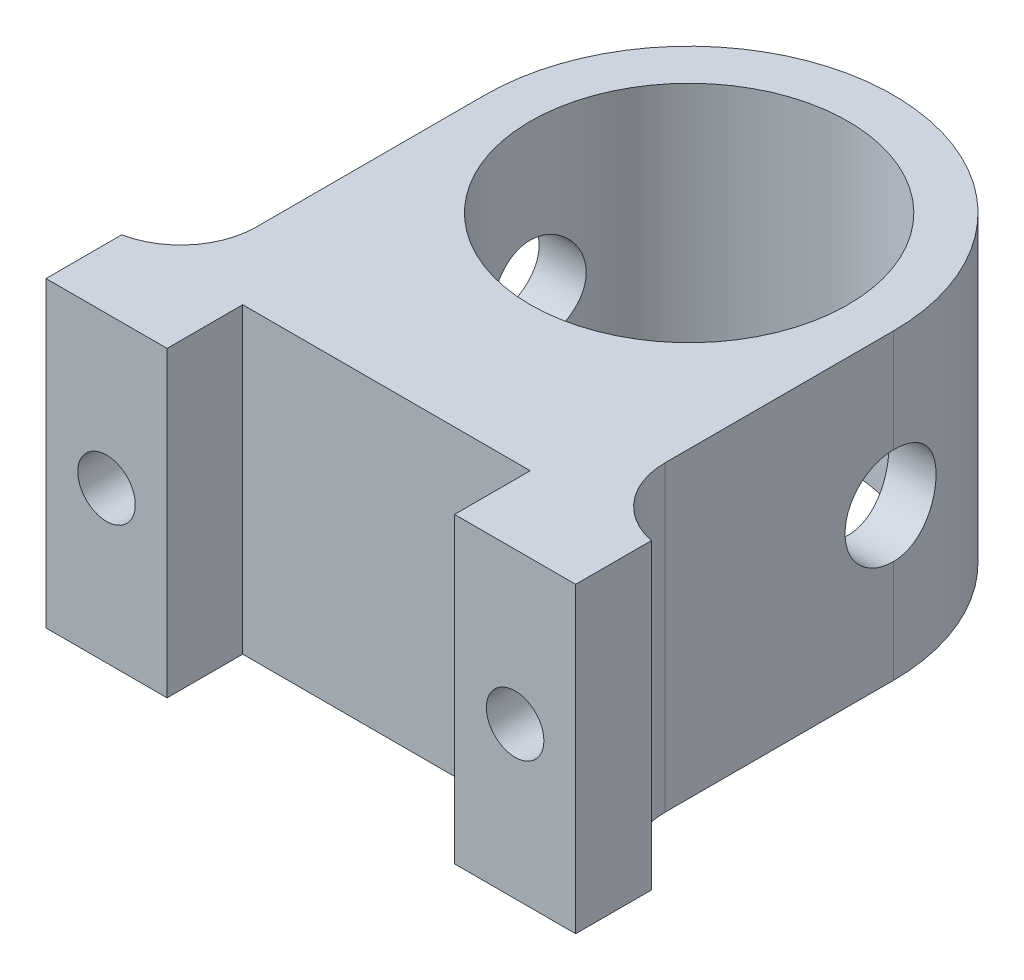
SolidWorks part; units mm, degrees
ref_plane "前视基准面" through (0, 0, 0) normal (0, 0, 1) x (1, 0, 0)
ref_plane "上视基准面" through (0, 0, 0) normal (0, 1, 0) x (1, 0, 0)
ref_plane "右视基准面" through (0, 0, 0) normal (1, 0, 0) x (0, 0, -1)
sketch "草图1" plane through (0, 0, 0) normal (0, 1, 0) x (1, 0, 0)
  circle A0 centre (0, 0) radius 10.5
  circle A1 centre (0, 0) radius 13.5
  dimension "D1" = 21
  dimension "D2" = 3
extrude "凸台-拉伸1" add sketch "草图1" along normal blind 20
ref_plane "基准面1" through (0, 0, 20) normal (0, 0, 1) x (1, 0, 0)
sketch "草图5" plane through (0, 0, 20) normal (0, 0, 1) x (1, 0, 0)
  line L0 (-13.5, 0) -> (-13.5, 20)
  line L1 (-13.5, 0) -> (13.5, 0)
  line L2 (0, 0) -> (0, 20) construction
  line L3 (-13.5, 20) -> (13.5, 20)
  line L4 (13.5, 0) -> (13.5, 20)
  dimension "D1" = 20
  dimension "D2" = 13.5
extrude "凸台-拉伸2" add sketch "草图5" against normal up to surface (20 mm away) up to face at (0, 20, 13.5)
sketch "草图2" plane through (0, 0, 0) normal (1, 0, 0) x (0, 0, -1)
  line L0 (-20, 0) -> (-10.5, 0)
  line L1 (10.5, 0) -> (13.5, 0)
  line L2 (10.5, 0) -> (13.5, 0) construction
  line L3 (-20, 0) -> (-10.5, 0) construction
  circle A0 centre (0, 10) radius 3.2
  dimension "D1" = 6.4
  dimension "D2" = 10
extrude "切除-拉伸2" cut sketch "草图2" against normal through all both and the other way through all
sketch "草图6" plane through (0, 0, 20) normal (0, 0, 1) x (1, 0, 0)
  line L0 (0, 0) -> (0, 20) construction
  line L1 (-13.5, 0) -> (13.5, 0) construction
  line L2 (13.5, 20) -> (-13.5, 20) construction
  line L3 (9.5, 0) -> (9.5, 20)
  line L4 (-9.5, 0) -> (-9.5, 20)
  line L5 (17.5, 0) -> (9.5, 0)
  line L9 (9.5, 0) -> (9.5, 20)
  line L11 (-9.5, 20) -> (-9.5, 0)
  line L14 (17.5, 0) -> (17.5, 20)
  line L15 (-17.5, 0) -> (-17.5, 20)
  line L16 (17.5, 20) -> (9.5, 20)
  line L17 (-9.5, 20) -> (-17.5, 20)
  line L18 (-9.5, 0) -> (-17.5, 0)
  line L19 (9.5, 0) -> (17.5, 0)
  line L20 (9.5, 20) -> (17.5, 20)
  line M2 (13.5, 0) -> (13.5, 20)
  line M3 (13.5, 20) -> (-13.5, 20)
  line M4 (-13.5, 20) -> (-13.5, 0)
  line M5 (-13.5, 0) -> (13.5, 0)
  dimension "D1" = 9.5
  dimension "D2" = 9.5
  dimension "D3" = 8
  dimension "D4" = 8
extrude "凸台-拉伸4" add sketch "草图6" along normal blind 5 contours L14 L16 L5 M2 | L3 M5 M2 M3 | L4 M5 M3 M4 | L18 L17 L15 M4 region at (11.5, 10, 20) region at (15.5, 10, 20) region at (-11.5, 10, 20) region at (-15.5, 10, 20)
fillet "圆角1" radius 5 2 edges at (13.5, 10, 20) (-13.5, 10, 20)
sketch "草图7" plane through (0, 0, 25) normal (0, 0, 1) x (1, 0, 0)
  line L0 (13.5, 0) -> (13.5, 20) construction
  line L1 (17.5, 0) -> (9.5, 0) construction
  line L2 (17.5, 20) -> (9.5, 20) construction
  line L3 (0, 0) -> (0, 19.5268) construction
  circle A0 centre (13.5, 10) radius 1.9
  circle A1 centre (-13.5, 10) radius 1.9
  dimension "D1" = 3.8
extrude "切除-拉伸3" cut sketch "草图7" against normal blind 5
